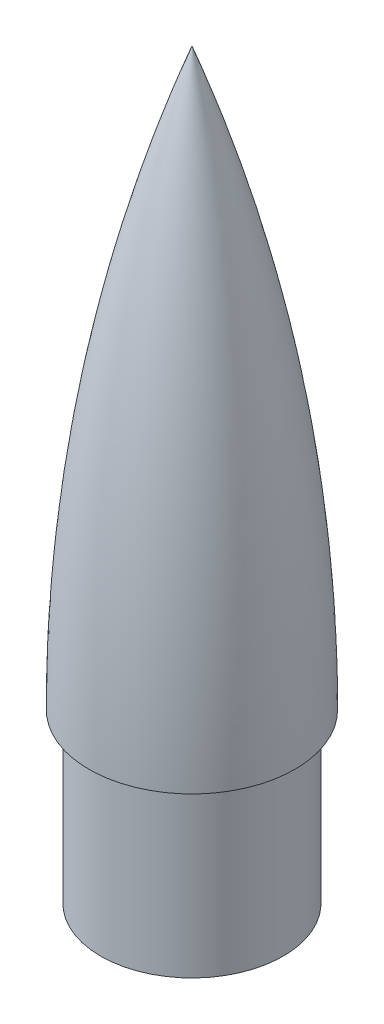
SolidWorks part; units mm, degrees
other "NoseCone"
ref_plane "Front Plane" through (0, 0, 0) normal (0, 0, 1) x (1, 0, 0)
ref_plane "Top Plane" through (0, 0, 0) normal (0, 1, 0) x (1, 0, 0)
ref_plane "Right Plane" through (0, 0, 0) normal (1, 0, 0) x (0, 0, -1)
sketch "Sketch1" plane through (0, 0, 0) normal (0, 0, 1) x (1, 0, 0)
  line L0 (0, -0.9433) -> (0, 351.1087) construction
  line L1 (-38.1, 0) -> (-34.1, 0)
  line L2 (-38.1, 0) -> (-38.1, 70)
  line L3 (-38.1, 70) -> (-43, 70)
  line L4 (-43, 4.6087) -> (-43, 50004.6087) construction
  line L5 (0, 298.2233) -> (0, 310)
  line L6 (-34.1, 0) -> (-34.1, 151.922)
  arc A0 (-43, 70) -> (0, 310) centre (648.2674, 70) cw
  arc A1 (-34.1, 151.922) -> (0, 298.2233) centre (648.2674, 70) cw
  dimension "D6" = 4
  dimension "D1" = 4
  dimension "D2" = 38.1
  dimension "D3" = 70
  dimension "D4" = 43
  dimension "D5" = 240
revolve "Cone" add sketch "Sketch1" angle 360 about L0
sketch "Sketch4" plane through (0, 0, 0) normal (0, -1, 0) x (1, 0, 0)
  line L0 (0, 0) -> (0, -50000) construction
  line L1 (15, 15.1) -> (-15, 15.1)
  line L2 (-15, 15.1) -> (-15, 30.6237)
  line L3 (15, 15.1) -> (15, 30.6237)
  line L4 (7.1801, 15.1) -> (-49992.8199, 15.1) construction
  circle A0 centre (0, 0) radius 34.1 construction
  arc A1 (-15, 30.6237) -> (15, 30.6237) centre (0, 0) ccw
  point P3 (0, 34.1)
  point P7 (0, 15.1)
  point P12 (15, 15.1)
  point P13 (15, 15.1)
  dimension "D2" = 19
extrude "Boss-Extrude2" add sketch "Sketch4" against normal blind 70 separate body contours A1 L3 L1 L2
fillet "Fillet1" radius 1 2 edges at (-15, 35, 15.1) (15, 35, 15.1)
shell "Shell1" thickness 2 removed face at (0, 0, 9.7516) removed face at (0, 70, 9.7516)
ref_plane "Plane2" through (-14, 70, 13.1) normal (0, -1, 0) x (-1, 0, 0)
sketch "Sketch5" plane through (0, 70, 0) normal (0, 1, 0) x (1, 0, 0)
  line L0 (-29.3053, -13.1) -> (29.3053, -13.1)
  line L2 (-29.3053, -13.1) -> (-31.4965, -11.1)
  line L3 (-31.4965, -11.1) -> (31.2452, -11.1)
  line L4 (31.2452, -11.1) -> (29.3053, -13.1)
  arc A0 (17, -27.2288) -> (-17, -27.2288) centre (0, 0) ccw construction
  dimension "D1" = 2
extrude "Boss-Extrude6" add sketch "Sketch5" against normal blind 69
